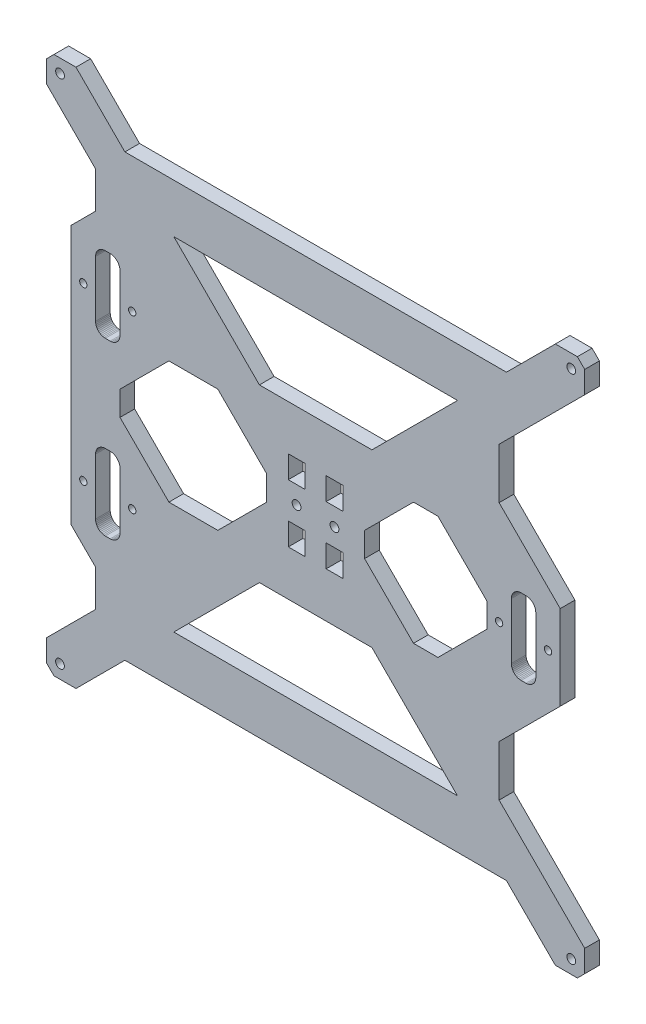
SolidWorks part; units mm, degrees
ref_plane "Plano frontal" through (0, 0, 0) normal (0, 0, 1) x (1, 0, 0)
ref_plane "Plano superior" through (0, 0, 0) normal (0, 1, 0) x (1, 0, 0)
ref_plane "Plano direito" through (0, 0, 0) normal (1, 0, 0) x (0, 0, -1)
sketch "Model" plane through (0, 0, 0) normal (0, 0, 1) x (1, 0, 0)
  line L0 (56.4801, 101.7809) -> (56.0108, 101.5495)
  line L1 (55.5758, 101.2588) -> (55.1824, 100.9139)
  line L2 (56.0108, 101.5495) -> (55.5758, 101.2588)
  line L3 (46.0108, 11.0855) -> (66.0108, 31.0855)
  line L4 (44.0108, 68.0854) -> (54.0108, 58.0854)
  line L5 (54.0108, 184.0854) -> (44.0108, 174.0854)
  line L6 (34.0108, 23.0855) -> (34.0108, 14.0855)
  line L7 (62.8392, 72.257) -> (63.1842, 72.6504)
  line L8 (61.5415, 101.7809) -> (61.0461, 101.9491)
  line L9 (61.0461, 101.9491) -> (60.5329, 102.0512)
  line L10 (60.5329, 102.0512) -> (60.0108, 102.0854)
  line L11 (34.0108, 14.0855) -> (37.0108, 11.0855)
  line L12 (63.9766, 74.5633) -> (64.0108, 75.0854)
  line L13 (60.5329, 71.1197) -> (61.0461, 71.2217)
  line L14 (56.4801, 71.3899) -> (56.9755, 71.2217)
  line L15 (56.0108, 71.6213) -> (56.4801, 71.3899)
  line L16 (254.0107, 219.0854) -> (219.0108, 184.0854)
  line L17 (62.0108, 101.5495) -> (61.5415, 101.7809)
  line L18 (54.3153, 99.6162) -> (54.1471, 99.1207)
  line L19 (54.1471, 99.1207) -> (54.045, 98.6075)
  line L20 (54.045, 98.6075) -> (54.0108, 98.0854)
  line L21 (58.0108, 102.0854) -> (60.0108, 102.0854)
  line L22 (242.0107, 11.0855) -> (222.0108, 31.0855)
  line L23 (46.0108, 231.0854) -> (66.0108, 211.0854)
  line L24 (55.5758, 71.912) -> (56.0108, 71.6213)
  line L25 (55.1824, 72.257) -> (55.5758, 71.912)
  line L26 (60.0108, 71.0854) -> (58.0108, 71.0854)
  line L27 (58.0108, 102.0854) -> (57.4887, 102.0512)
  line L28 (57.4887, 102.0512) -> (56.9755, 101.9491)
  line L29 (54.0108, 75.0854) -> (54.0108, 98.0854)
  line L30 (54.0108, 75.0854) -> (54.045, 74.5633)
  line L31 (54.045, 74.5633) -> (54.1471, 74.0502)
  line L32 (34.0108, 219.0854) -> (54.0108, 199.0854)
  line L33 (63.8745, 99.1207) -> (63.7063, 99.6162)
  line L34 (63.9766, 98.6075) -> (63.8745, 99.1207)
  line L35 (64.0108, 98.0854) -> (63.9766, 98.6075)
  line L36 (37.0108, 231.0854) -> (34.0108, 228.0854)
  line L37 (251.0107, 231.0854) -> (242.0107, 231.0854)
  line L38 (44.0108, 174.0854) -> (44.0108, 68.0854)
  line L39 (63.7063, 99.6162) -> (63.4749, 100.0854)
  line L40 (63.4749, 100.0854) -> (63.1842, 100.5205)
  line L41 (254.0107, 23.0855) -> (254.0107, 14.0855)
  line L42 (54.0108, 43.0855) -> (54.0108, 58.0854)
  line L43 (54.3153, 73.5547) -> (54.5467, 73.0854)
  line L44 (54.5467, 73.0854) -> (54.8374, 72.6504)
  line L45 (63.1842, 100.5205) -> (62.8392, 100.9139)
  line L46 (54.8374, 72.6504) -> (55.1824, 72.257)
  line L47 (64.0108, 98.0854) -> (64.0108, 75.0854)
  line L48 (54.5467, 100.0854) -> (54.3153, 99.6162)
  line L49 (61.5415, 71.3899) -> (62.0108, 71.6213)
  line L50 (62.0108, 71.6213) -> (62.4458, 71.912)
  line L51 (62.4458, 71.912) -> (62.8392, 72.257)
  line L52 (61.0461, 71.2217) -> (61.5415, 71.3899)
  line L53 (251.0107, 11.0855) -> (254.0107, 14.0855)
  line L54 (63.7063, 73.5547) -> (63.8745, 74.0502)
  line L55 (63.8745, 74.0502) -> (63.9766, 74.5633)
  line L56 (62.4458, 101.2588) -> (62.0108, 101.5495)
  line L57 (62.8392, 100.9139) -> (62.4458, 101.2588)
  line L58 (242.0107, 231.0854) -> (222.0108, 211.0854)
  line L59 (34.0108, 23.0855) -> (54.0108, 43.0855)
  line L60 (54.0108, 199.0854) -> (54.0108, 184.0854)
  line L61 (56.9755, 101.9491) -> (56.4801, 101.7809)
  line L62 (254.0107, 228.0854) -> (251.0107, 231.0854)
  line L63 (60.0108, 71.0854) -> (60.5329, 71.1197)
  line L64 (56.9755, 71.2217) -> (57.4887, 71.1197)
  line L65 (54.8374, 100.5205) -> (54.5467, 100.0854)
  line L66 (55.1824, 100.9139) -> (54.8374, 100.5205)
  line L67 (63.1842, 72.6504) -> (63.4749, 73.0854)
  line L68 (63.4749, 73.0854) -> (63.7063, 73.5547)
  line L69 (54.1471, 74.0502) -> (54.3153, 73.5547)
  line L70 (57.4887, 71.1197) -> (58.0108, 71.0854)
  line L71 (66.0108, 211.0854) -> (222.0108, 211.0854)
  line L72 (219.0108, 58.0854) -> (219.0108, 78.8116)
  line L73 (66.0108, 31.0855) -> (222.0108, 31.0855)
  line L74 (219.0108, 163.3887) -> (219.0108, 184.0854)
  line L75 (226.48, 135.6438) -> (226.0108, 135.4124)
  line L76 (63.8745, 169.1277) -> (63.7063, 169.6232)
  line L77 (63.7063, 169.6232) -> (63.4749, 170.0924)
  line L78 (226.0108, 135.4124) -> (225.5757, 135.1217)
  line L79 (63.1842, 170.5275) -> (62.8392, 170.9209)
  line L80 (226.9755, 135.812) -> (226.48, 135.6438)
  line L81 (227.4886, 135.9141) -> (226.9755, 135.812)
  line L82 (228.0108, 135.9483) -> (227.4886, 135.9141)
  line L83 (228.0108, 135.9483) -> (230.0107, 135.9483)
  line L84 (230.5329, 135.9141) -> (230.0107, 135.9483)
  line L85 (231.046, 135.812) -> (230.5329, 135.9141)
  line L86 (231.5415, 135.6438) -> (231.046, 135.812)
  line L87 (232.0107, 135.4124) -> (231.5415, 135.6438)
  line L88 (232.4458, 135.1217) -> (232.0107, 135.4124)
  line L89 (232.8392, 134.7767) -> (232.4458, 135.1217)
  line L90 (233.1842, 134.3833) -> (232.8392, 134.7767)
  line L91 (233.4749, 133.9483) -> (233.1842, 134.3833)
  line L92 (233.7063, 133.479) -> (233.4749, 133.9483)
  line L93 (233.8745, 132.9836) -> (233.7063, 133.479)
  line L94 (233.9765, 132.4704) -> (233.8745, 132.9836)
  line L95 (234.0107, 131.9483) -> (233.9765, 132.4704)
  line L96 (234.0107, 131.9483) -> (234.0107, 108.9483)
  line L97 (233.9765, 108.4262) -> (234.0107, 108.9483)
  line L98 (233.8745, 107.913) -> (233.9765, 108.4262)
  line L99 (233.7063, 107.4176) -> (233.8745, 107.913)
  line L100 (233.4749, 106.9483) -> (233.7063, 107.4176)
  line L101 (233.1842, 106.5133) -> (233.4749, 106.9483)
  line L102 (232.8392, 106.1199) -> (233.1842, 106.5133)
  line L103 (232.4458, 105.7749) -> (232.8392, 106.1199)
  line L104 (232.0107, 105.4842) -> (232.4458, 105.7749)
  line L105 (231.5415, 105.2528) -> (232.0107, 105.4842)
  line L106 (231.046, 105.0846) -> (231.5415, 105.2528)
  line L107 (230.5329, 104.9825) -> (231.046, 105.0846)
  line L108 (230.0107, 104.9483) -> (230.5329, 104.9825)
  line L109 (230.0107, 104.9483) -> (228.0108, 104.9483)
  line L110 (227.4886, 104.9825) -> (228.0108, 104.9483)
  line L111 (226.9755, 105.0846) -> (227.4886, 104.9825)
  line L112 (226.48, 105.2528) -> (226.9755, 105.0846)
  line L113 (226.0108, 105.4842) -> (226.48, 105.2528)
  line L114 (225.5757, 105.7749) -> (226.0108, 105.4842)
  line L115 (225.1823, 106.1199) -> (225.5757, 105.7749)
  line L116 (224.8373, 106.5133) -> (225.1823, 106.1199)
  line L117 (224.5466, 106.9483) -> (224.8373, 106.5133)
  line L118 (224.3152, 107.4176) -> (224.5466, 106.9483)
  line L119 (224.147, 107.913) -> (224.3152, 107.4176)
  line L120 (224.045, 108.4262) -> (224.147, 107.913)
  line L121 (224.0108, 108.9483) -> (224.045, 108.4262)
  line L122 (224.0108, 108.9483) -> (224.0108, 131.9483)
  line L123 (224.045, 132.4704) -> (224.0108, 131.9483)
  line L124 (224.147, 132.9836) -> (224.045, 132.4704)
  line L125 (224.3152, 133.479) -> (224.147, 132.9836)
  line L126 (224.5466, 133.9483) -> (224.3152, 133.479)
  line L127 (224.8373, 134.3833) -> (224.5466, 133.9483)
  line L128 (225.1823, 134.7767) -> (224.8373, 134.3833)
  line L129 (225.5757, 135.1217) -> (225.1823, 134.7767)
  line L130 (63.9766, 168.6146) -> (63.8745, 169.1277)
  line L131 (64.0108, 168.0924) -> (63.9766, 168.6146)
  line L132 (64.0108, 168.0924) -> (64.0108, 145.0925)
  line L133 (63.9766, 144.5704) -> (64.0108, 145.0925)
  line L134 (63.8745, 144.0572) -> (63.9766, 144.5704)
  line L135 (63.7063, 143.5617) -> (63.8745, 144.0572)
  line L136 (63.4749, 143.0925) -> (63.7063, 143.5617)
  line L137 (63.1842, 142.6574) -> (63.4749, 143.0925)
  line L138 (62.8392, 142.264) -> (63.1842, 142.6574)
  line L139 (62.4458, 141.919) -> (62.8392, 142.264)
  line L140 (62.0108, 141.6284) -> (62.4458, 141.919)
  line L141 (61.5415, 141.3969) -> (62.0108, 141.6284)
  line L142 (61.0461, 141.2288) -> (61.5415, 141.3969)
  line L143 (60.5329, 141.1267) -> (61.0461, 141.2288)
  line L144 (60.0108, 141.0925) -> (60.5329, 141.1267)
  line L145 (60.0108, 141.0925) -> (58.0108, 141.0925)
  line L146 (57.4887, 141.1267) -> (58.0108, 141.0925)
  line L147 (56.9755, 141.2288) -> (57.4887, 141.1267)
  line L148 (56.4801, 141.3969) -> (56.9755, 141.2288)
  line L149 (56.0108, 141.6284) -> (56.4801, 141.3969)
  line L150 (55.5758, 141.919) -> (56.0108, 141.6284)
  line L151 (55.1824, 142.264) -> (55.5758, 141.919)
  line L152 (54.8374, 142.6574) -> (55.1824, 142.264)
  line L153 (54.5467, 143.0925) -> (54.8374, 142.6574)
  line L154 (54.3153, 143.5617) -> (54.5467, 143.0925)
  line L155 (54.1471, 144.0572) -> (54.3153, 143.5617)
  line L156 (54.045, 144.5704) -> (54.1471, 144.0572)
  line L157 (54.0108, 145.0925) -> (54.045, 144.5704)
  line L158 (54.0108, 145.0925) -> (54.0108, 168.0924)
  line L159 (54.045, 168.6146) -> (54.0108, 168.0924)
  line L160 (54.1471, 169.1277) -> (54.045, 168.6146)
  line L161 (54.3153, 169.6232) -> (54.1471, 169.1277)
  line L162 (54.5467, 170.0924) -> (54.3153, 169.6232)
  line L163 (54.8374, 170.5275) -> (54.5467, 170.0924)
  line L164 (55.1824, 170.9209) -> (54.8374, 170.5275)
  line L165 (55.5758, 171.2659) -> (55.1824, 170.9209)
  line L166 (56.0108, 171.5565) -> (55.5758, 171.2659)
  line L167 (56.4801, 171.788) -> (56.0108, 171.5565)
  line L168 (56.9755, 171.9561) -> (56.4801, 171.788)
  line L169 (57.4887, 172.0582) -> (56.9755, 171.9561)
  line L170 (58.0108, 172.0924) -> (57.4887, 172.0582)
  line L171 (58.0108, 172.0924) -> (60.0108, 172.0924)
  line L172 (60.5329, 172.0582) -> (60.0108, 172.0924)
  line L173 (61.0461, 171.9561) -> (60.5329, 172.0582)
  line L174 (61.5415, 171.788) -> (61.0461, 171.9561)
  line L175 (62.0108, 171.5565) -> (61.5415, 171.788)
  line L176 (62.4458, 171.2659) -> (62.0108, 171.5565)
  line L177 (62.8392, 170.9209) -> (62.4458, 171.2659)
  line L178 (63.4749, 170.0924) -> (63.1842, 170.5275)
  line L179 (86.0108, 191.0854) -> (202.0108, 191.0854)
  line L180 (202.0108, 191.0854) -> (167.0108, 156.0854)
  line L181 (167.0108, 156.0854) -> (121.0108, 156.0854)
  line L182 (86.0108, 191.0854) -> (121.0108, 156.0854)
  line L183 (124.0108, 126.0854) -> (124.0108, 116.0854)
  line L184 (124.0108, 116.0854) -> (104.0108, 96.0854)
  line L185 (104.0108, 96.0854) -> (84.0108, 96.0854)
  line L186 (84.0108, 96.0854) -> (64.0108, 116.0854)
  line L187 (64.0108, 116.0854) -> (64.0108, 126.0854)
  line L188 (64.0108, 126.0854) -> (84.0108, 146.0854)
  line L189 (84.0108, 146.0854) -> (104.0108, 146.0854)
  line L190 (104.0108, 146.0854) -> (124.0108, 126.0854)
  line L191 (214.0108, 126.0854) -> (214.0108, 116.0854)
  line L192 (194.0108, 96.0854) -> (184.0108, 96.0854)
  line L193 (184.0108, 96.0854) -> (164.0108, 116.0854)
  line L194 (164.0108, 116.0854) -> (164.0108, 126.0854)
  line L195 (164.0108, 126.0854) -> (184.0108, 146.0854)
  line L196 (184.0108, 146.0854) -> (194.0108, 146.0854)
  line L197 (121.0108, 86.0854) -> (86.0108, 51.0854)
  line L198 (167.0108, 86.0854) -> (121.0108, 86.0854)
  line L199 (202.0108, 51.0854) -> (167.0108, 86.0854)
  line L200 (86.0108, 51.0854) -> (202.0108, 51.0854)
  line L201 (132.8089, 113.819) -> (132.8089, 104.619)
  line L202 (132.8089, 137.619) -> (132.8089, 128.419)
  line L203 (139.6089, 104.619) -> (139.6089, 113.819)
  line L204 (139.6089, 113.819) -> (132.8089, 113.819)
  line L205 (139.6089, 137.619) -> (132.8089, 137.619)
  line L206 (132.8089, 128.419) -> (139.6089, 128.419)
  line L207 (139.6089, 128.419) -> (139.6089, 137.619)
  line L208 (132.8089, 104.619) -> (139.6089, 104.619)
  line L209 (155.1065, 104.6039) -> (155.1065, 113.8039)
  line L210 (148.3064, 137.6039) -> (148.3064, 128.4039)
  line L211 (155.1065, 137.6039) -> (148.3064, 137.6039)
  line L212 (148.3064, 104.6039) -> (155.1065, 104.6039)
  line L213 (155.1065, 128.4039) -> (155.1065, 137.6039)
  line L214 (155.1065, 113.8039) -> (148.3064, 113.8039)
  line L215 (148.3064, 128.4039) -> (155.1065, 128.4039)
  line L216 (148.3064, 113.8039) -> (148.3064, 104.6039)
  line L217 (34.0108, 228.0854) -> (34.0108, 219.0854)
  line L218 (219.0108, 58.0854) -> (254.0107, 23.0855)
  line L219 (254.0107, 228.0854) -> (254.0107, 219.0854)
  line L220 (46.0108, 231.0854) -> (37.0108, 231.0854)
  line L221 (251.0107, 11.0855) -> (242.0107, 11.0855)
  line L222 (37.0108, 11.0855) -> (46.0108, 11.0855)
  line L223 (244.0107, 138.3887) -> (219.0108, 163.3887)
  line L224 (244.0107, 103.8116) -> (219.0108, 78.8116)
  line L225 (214.0108, 116.0854) -> (194.0108, 96.0854)
  line L226 (194.0108, 146.0854) -> (214.0108, 126.0854)
  line L227 (204.0811, 106.1558) -> (204.0811, 106.0854)
  line L228 (104.0108, 146.0854) -> (104.0811, 146.0854)
  line L229 (204.0811, 136.0854) -> (204.0811, 136.0151)
  line L230 (244.0107, 138.3887) -> (244.0107, 103.8116)
  circle A0 centre (69.0108, 86.0727) radius 1.5
  circle A1 centre (49.0108, 86.0854) radius 1.5
  circle A2 centre (69.0108, 156.0854) radius 1.5
  circle A3 centre (49.0108, 156.0854) radius 1.5
  circle A4 centre (39.5004, 225.5958) radius 1.8
  circle A5 centre (248.5211, 225.5958) radius 1.8
  circle A6 centre (136.2069, 121.1346) radius 1.8
  circle A7 centre (151.7045, 121.1195) radius 1.8
  circle A8 centre (219.0108, 121.1155) radius 1.5
  circle A9 centre (239.0107, 121.0854) radius 1.5
  circle A10 centre (248.5211, 16.5751) radius 1.8
  circle A11 centre (39.4803, 16.5934) radius 1.8
extrude "Ressalto-extrusão1" add sketch "Model" along normal blind 6 contours L230 L223 L74 L16 L219 L62 L37 L58 L71 L23 L220 L36 L217 L32 L60 L5 L38 L4 L42 L59 L6 L11 L222 L3 L73 L22 L221 L53 L41 L218 L72 L224 A11 A10 A9 A8 A7 A6 A5 A4 A3 region at (139.9534, 121.0815, 0)
ref_axis "Eixo1" through (219.0108, 121.1155, 6) along (0, 0, -1)
ref_axis "Eixo2" through (239.0107, 121.0854, 6) along (0, 0, -1)
ref_plane "Plano1" through (0.1829, 121.4451, 0) normal (0.0015, 1, 0) x (1, -0.0015, 0)
ref_axis "Eixo3" through (49.0108, 156.0854, 6) along (0, 0, -1)
ref_axis "Eixo4" through (69.0108, 156.0854, 6) along (0, 0, -1)
ref_plane "Plano2" through (0, 156.0854, 0) normal (0, 1, 0) x (1, 0, 0)
ref_axis "Eixo5" through (69.0108, 86.0727, 6) along (0, 0, -1)
ref_axis "Eixo6" through (49.0108, 86.0854, 6) along (0, 0, -1)
ref_plane "Plano3" through (0.055, 86.1167, 0) normal (-0.0006, -1, 0) x (-1, 0.0006, 0)
ref_plane "Plano4" through (59.0108, 0, 0) normal (1, 0, 0) x (0, 0, -1)
ref_plane "Plano5" through (229.0108, 0, 0) normal (-1, 0, 0) x (0, 0, 1)
